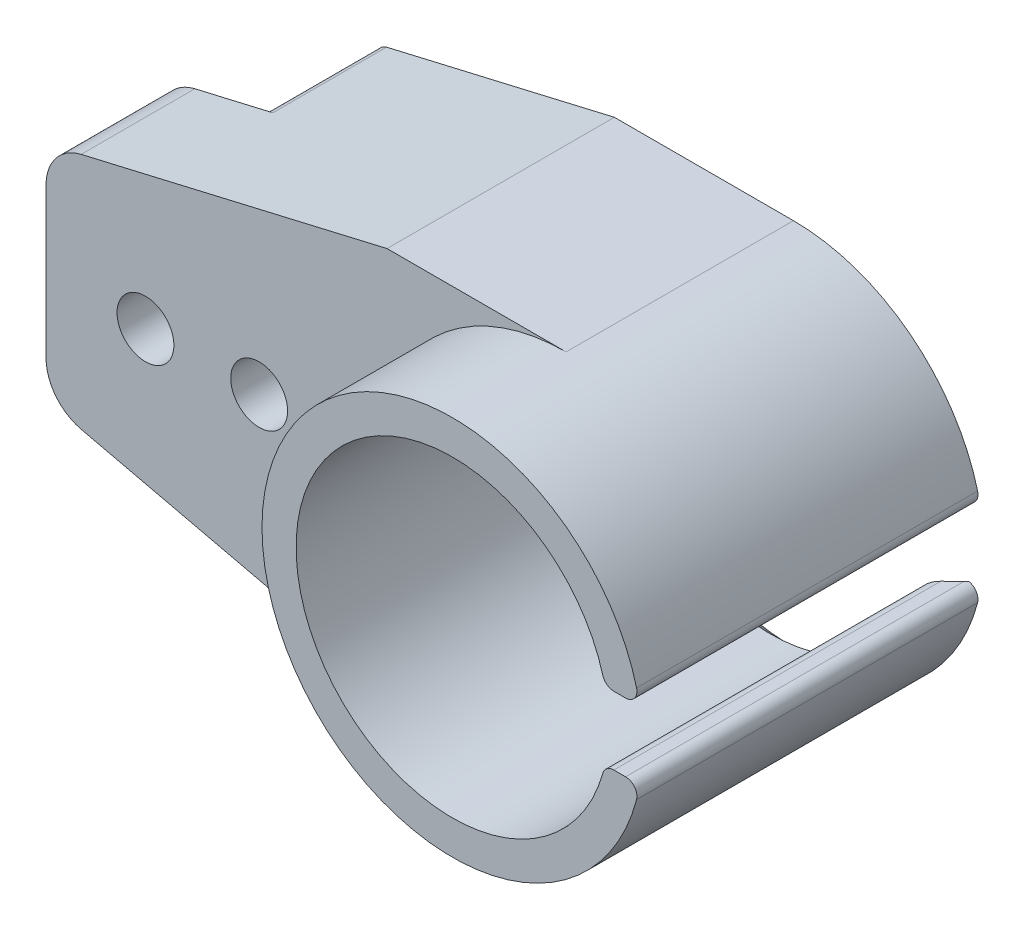
SolidWorks part; units mm, degrees
ref_plane "Plan de face" through (0, 0, 0) normal (0, 0, 1) x (1, 0, 0)
ref_plane "Plan de dessus" through (0, 0, 0) normal (0, 1, 0) x (1, 0, 0)
ref_plane "Plan de droite" through (0, 0, 0) normal (1, 0, 0) x (0, 0, -1)
sketch "Esquisse1" plane through (0, 0, 0) normal (0, 0, 1) x (1, 0, 0)
  line L0 (0, 0) -> (13.75, 0) construction
  line L1 (0, 3) -> (21.7672, 3) construction
  line L2 (0, -3) -> (21.7672, -3) construction
  line L3 (13.4187, 3) -> (16.4792, 3)
  line L4 (16.4792, -3) -> (13.4187, -3)
  line L5 (0, 0) -> (0, 16.75) construction
  line L6 (0, -16.75) -> (-45.75, -16.75)
  line L7 (-45.75, -16.75) -> (-45.75, 16.75)
  line L8 (-45.75, 16.75) -> (0, 16.75)
  circle A0 centre (0, 0) radius 13.75 construction
  arc A1 (13.4187, 3) -> (13.4187, -3) centre (0, 0) ccw
  arc A3 (16.4792, 3) -> (0, 16.75) centre (0, 0) ccw
  arc A4 (16.4792, -3) -> (0, -16.75) centre (0, 0) cw
  circle A5 centre (-37, 0) radius 2.5
  circle A6 centre (-27, 0) radius 2.5
  point P18 (-13.75, 0)
  dimension "D1" = 27.5
  dimension "D2" = 6
  dimension "D3" = 32
  dimension "D4" = 3
  dimension "D6" = 5
  dimension "D5" = 10
  dimension "D7" = 27
extrude "Boss.-Extru.1" add sketch "Esquisse1" along normal blind 30
chamfer "Chanfrein1" distance 2 angle 45 1 edges at (-13.75, 0, 0)
fillet "Congé2" radius 1 4 edges at (16.4792, -3, 15) (16.4792, 3, 15) (13.4187, -3, 16) (13.4187, 3, 16)
sketch "Esquisse2" plane through (0, 0, 0) normal (0, 0, -1) x (-1, 0, 0)
  line L0 (45.75, 10.1) -> (27, 10.1)
  line L1 (45.75, 16.75) -> (45.75, -16.75) construction
  line L2 (27, -10.1) -> (45.75, -10.1)
  line L3 (45.75, -10.1) -> (45.75, 10.1)
  arc A0 (27, 10.1) -> (27, -10.1) centre (27, 0) ccw
  circle A1 centre (27, 0) radius 2.5 construction
  dimension "D1" = 20.2
extrude "Enlèv. mat.-Extru.1" cut sketch "Esquisse2" against normal blind 10
sketch "Esquisse3" plane through (0, 0, 30) normal (0, 0, 1) x (1, 0, 0)
  line L0 (0, 16.75) -> (-45.75, 16.75) construction
  line L1 (0, 16.75) -> (-45.75, 16.75)
  line L2 (-45.75, 16.75) -> (-45.75, -16.75)
  line L3 (-45.75, -16.75) -> (0, -16.75)
  line L4 (-45.75, 16.75) -> (-45.75, -16.75) construction
  arc A1 (0, 16.75) -> (0, -16.75) centre (0, 0) ccw
  arc A2 (16.2008, 4.254) -> (0, 16.75) centre (0, 0) ccw construction
  arc A3 (0, -16.75) -> (16.2008, -4.254) centre (0, 0) ccw construction
extrude "Enlèv. mat.-Extru.2" cut sketch "Esquisse3" against normal blind 10
sketch "Esquisse5" plane through (0, 0, 20) normal (0, 0, 1) x (1, 0, 0)
  line L0 (-15.75, 16.75) -> (-45.75, 9.75)
  line L1 (0, 16.75) -> (-45.75, 16.75) construction
  line L2 (-45.75, 16.75) -> (-45.75, -16.75) construction
  line L3 (-45.75, 9.75) -> (-45.75, 16.75)
  line L4 (-45.75, 16.75) -> (-15.75, 16.75)
  line L5 (-45.75, 0) -> (0, 0) construction
  line L6 (-45.75, -16.75) -> (-15.75, -16.75)
  line L7 (-45.75, -9.75) -> (-45.75, -16.75)
  line L8 (-15.75, -16.75) -> (-45.75, -9.75)
  dimension "D1" = 7
  dimension "D2" = 30
extrude "Enlèv. mat.-Extru.3" cut sketch "Esquisse5" against normal through all
fillet "Congé3" radius 1 2 edges at (-44.25, 10.1, 5) (-44.25, -10.1, 5)
fillet "Congé4" radius 4 2 edges at (-45.75, 9.75, 15) (-45.75, -9.75, 15)
sketch "Esquisse6" plane through (0, 0, 0) normal (0, 0, -1) x (-1, 0, 0)
  line L0 (27, 10.1) -> (47.1758, 10.1)
  line L1 (47.1758, 10.1) -> (47.1758, 16.1)
  line L2 (47.1758, 16.1) -> (9.3302, 16.1)
  line L4 (9.3302, 10.1) -> (27, 10.1)
  line L6 (4.1408, 13.1117) -> (9.3302, 10.1)
  line L7 (4.1408, 13.1117) -> (9.3302, 16.1)
  line L8 (9.3302, 16.1) -> (9.3302, 10.1) construction
  arc A1 (-13.2347, -3.7288) -> (-13.2347, 3.7288) centre (0, 0) ccw construction
  dimension "D1" = 6
  dimension "D2" = 6
